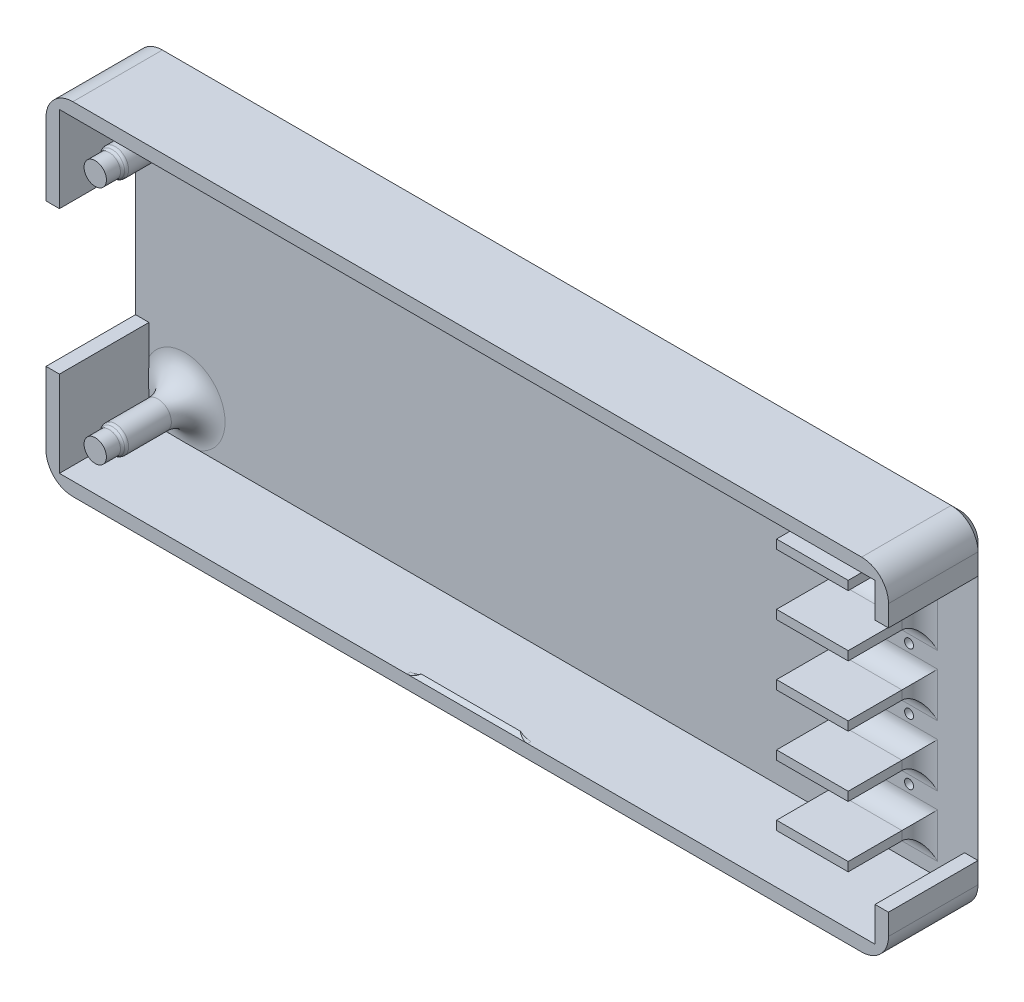
SolidWorks part; units mm, degrees
ref_plane "Front Plane" through (0, 0, 0) normal (0, 0, 1) x (1, 0, 0)
ref_plane "Top Plane" through (0, 0, 0) normal (0, 1, 0) x (1, 0, 0)
ref_plane "Right Plane" through (0, 0, 0) normal (1, 0, 0) x (0, 0, -1)
sketch "Sketch1" plane through (0, 0, 0) normal (0, 0, 1) x (1, 0, 0)
  line L0 (-1.5, 36.7) -> (92.6, 36.7)
  line L1 (0, 0) -> (91.1, 0)
  line L2 (0, 0) -> (0, 35.2)
  line L3 (0, 35.2) -> (91.1, 35.2)
  line L4 (91.1, 0) -> (91.1, 35.2)
  line L5 (92.6, -1.5) -> (92.6, 36.7)
  line L6 (-1.5, -1.5) -> (92.6, -1.5)
  line L7 (-1.5, -1.5) -> (-1.5, 36.7)
  dimension "D1" = 91.1
  dimension "D2" = 35.2
  dimension "D3" = 1.5
extrude "Boss-Extrude1" add sketch "Sketch1" along normal blind 1 contours L1 L4 L3 L2 | L7 L6 L5 L0 L4 L1 L2 L3 region at (45.55, 35.6844, 0) region at (45.55, 17.6, 0)
extrude "Boss-Extrude2" add sketch "Sketch1<3>" along normal blind 11
sketch "Sketch1<3>" plane through (0, 0, 0) normal (0, 0, 1) x (1, 0, 0) same geometry as "Sketch1"
sketch "Sketch2" plane through (0, 0, 11) normal (0, 0, 1) x (1, 0, 0)
  line L0 (-1.5, 36.7) -> (-1.5, -1.5) construction
  line L1 (-1.5, 25.6) -> (0, 25.6)
  line L2 (-1.5, 25.6) -> (-1.5, 9.6)
  line L3 (-1.5, 9.6) -> (0, 9.6)
  line L4 (0, 25.6) -> (0, 9.6)
  line L5 (92.6, -1.5) -> (92.6, 36.7) construction
  line L6 (92.6, 31.35) -> (91.1, 31.35)
  line L7 (92.6, 31.35) -> (92.6, 3.85)
  line L8 (92.6, 3.85) -> (91.1, 3.85)
  line L9 (91.1, 31.35) -> (91.1, 3.85)
  line L10 (-0.75, 25.6) -> (-0.75, 35.2) construction
  line L12 (-0.75, 9.6) -> (-0.75, 0) construction
  line L13 (91.1, 0) -> (0, 0) construction
  line L14 (91.85, 3.85) -> (91.85, 0) construction
  line L15 (91.85, 31.35) -> (91.85, 35.2) construction
  line L16 (91.1, 35.2) -> (0, 35.2) construction
  line L17 (0, 35.2) -> (0, 0) construction
  line L18 (91.1, 0) -> (91.1, 35.2) construction
  dimension "D1" = 16
  dimension "D2" = 27.5
extrude "Cut-Extrude1" cut sketch "Sketch2" against normal blind 10
sketch "Sketch3" plane through (0, 0, 1) normal (0, 0, 1) x (1, 0, 0)
  line L0 (92.6, 3.85) -> (92.6, 31.35) construction
  line L1 (78.1, 31.7) -> (86.1, 31.7)
  line L2 (78.1, 31.7) -> (78.1, 30.7)
  line L3 (78.1, 30.7) -> (86.1, 30.7)
  line L4 (86.1, 31.7) -> (86.1, 30.7)
  line L5 (0, 35.2) -> (91.1, 35.2) construction
  line L6 (78.1, 24.9) -> (86.1, 24.9)
  line L7 (78.1, 24.9) -> (78.1, 23.9)
  line L8 (78.1, 23.9) -> (86.1, 23.9)
  line L9 (86.1, 24.9) -> (86.1, 23.9)
  line L10 (78.1, 18.1) -> (86.1, 18.1)
  line L11 (78.1, 18.1) -> (78.1, 17.1)
  line L12 (78.1, 17.1) -> (86.1, 17.1)
  line L13 (86.1, 18.1) -> (86.1, 17.1)
  line L15 (78.1, 11.3) -> (86.1, 11.3)
  line L16 (78.1, 11.3) -> (78.1, 10.3)
  line L17 (78.1, 10.3) -> (86.1, 10.3)
  line L18 (86.1, 11.3) -> (86.1, 10.3)
  line L19 (78.1, 4.5) -> (86.1, 4.5)
  line L20 (78.1, 4.5) -> (78.1, 3.5)
  line L21 (78.1, 3.5) -> (86.1, 3.5)
  line L22 (86.1, 4.5) -> (86.1, 3.5)
  line L23 (91.1, 0) -> (0, 0) construction
  dimension "D1" = 1
  dimension "D2" = 6.5
  dimension "D3" = 3.5
  dimension "D4" = 8
  dimension "D6" = 3.5
  dimension "D7" = 6.8
  dimension "D5" = 5
extrude "Boss-Extrude3" add sketch "Sketch3" along normal blind 8
sketch "Sketch4" plane through (0, 0, 1) normal (0, 0, 1) x (1, 0, 0)
  line L0 (84.9, 35.2) -> (84.9, 0) construction
  line L1 (91.1, 35.2) -> (0, 35.2) construction
  line L2 (0, 0) -> (91.1, 0) construction
  line L5 (86.1, 31.7) -> (78.1, 31.7) construction
  line L7 (92.6, 3.85) -> (92.6, 31.35) construction
  line L8 (84.9, 7.4) -> (86.1, 4.5) construction
  line L9 (84.9, 7.4) -> (86.1, 10.3) construction
  line L10 (84.9, 27.8) -> (86.1, 24.9) construction
  line L11 (84.9, 27.8) -> (86.1, 30.7) construction
  circle A0 centre (84.9, 27.8) radius 0.5
  circle A1 centre (84.9, 21) radius 0.5
  circle A2 centre (84.9, 14.2) radius 0.5
  circle A3 centre (84.9, 7.4) radius 0.5
  dimension "D1" = 1
  dimension "D6" = 3.9
  dimension "D9" = 7.7
  dimension "D10" = 6.8
  dimension "D11" = 6.8
  dimension "D3" = 4
extrude "Cut-Extrude2" cut sketch "Sketch4" against normal blind 10
sketch "Sketch5" plane through (0, 0, 1) normal (0, 0, 1) x (1, 0, 0)
  line L0 (4, 35.2) -> (4, 0) construction
  line L1 (91.1, 35.2) -> (0, 35.2) construction
  line L2 (0, 0) -> (91.1, 0) construction
  line L4 (0, 35.2) -> (0, 25.6) construction
  line L5 (0, 35.2) -> (91.1, 35.2) construction
  line L6 (91.1, 0) -> (0, 0) construction
  circle A0 centre (4, 31) radius 1.5
  circle A1 centre (4, 4.2) radius 1.5
  dimension "D4" = 3
  dimension "D1" = 4
  dimension "D2" = 4.2
  dimension "D3" = 4.2
extrude "Boss-Extrude4" add sketch "Sketch5" along normal blind 8
sketch "Sketch7" plane through (0, 0, 9) normal (0, 0, 1) x (1, 0, 0)
  circle A0 centre (4, 31) radius 1.25
  circle A1 centre (4, 4.2) radius 1.25
  circle A2 centre (4, 31) radius 1.5 construction
  circle A3 centre (4, 4.2) radius 1.5 construction
  dimension "D1" = 2.5
extrude "Boss-Extrude6" add sketch "Sketch7" along normal blind 2
fillet "Fillet1" radius 3 2 edges at (5.5, 4.2, 1) (5.5, 31, 1)
fillet "Fillet2" radius 2 20 edges at (78.1, 31.2, 1) (82.1, 30.7, 1) (86.1, 31.2, 1) (82.1, 31.7, 1) (78.1, 4, 1) (82.1, 3.5, 1) (86.1, 4, 1) (78.1, 10.8, 1) (82.1, 10.3, 1) (86.1, 10.8, 1) (82.1, 11.3, 1) (78.1, 17.6, 1) (82.1, 17.1, 1) (86.1, 17.6, 1) (82.1, 18.1, 1) (78.1, 24.4, 1) (82.1, 23.9, 1) (86.1, 24.4, 1) (82.1, 24.9, 1) (82.1, 4.5, 1)
fillet "Fillet3" radius 3 4 edges at (-1.5, 36.7, 5.5) (92.6, 36.7, 5.5) (-1.5, -1.5, 5.5) (92.6, -1.5, 5.5)
chamfer "Chamfer2" distance 1 angle 45 8 edges at (-1.5, 17.6, 0) (-0.6213, -0.6213, 0) (-0.6213, 35.8213, 0) (45.55, -1.5, 0) (45.55, 36.7, 0) (91.7213, -0.6213, 0) (91.7213, 35.8213, 0) (92.6, 17.6, 0)
sketch "Sketch6" plane through (0, 35.2, 0) normal (0, -1, 0) x (1, 0, 0)
  line L0 (1.5, 11) -> (89.6, 11) construction
  line L1 (40.55, 11) -> (50.55, 11)
  line L2 (40.55, 11) -> (40.55, 10.6)
  line L3 (40.55, 10.6) -> (50.55, 10.6)
  line L4 (50.55, 11) -> (50.55, 10.6)
  line L5 (-1.5, 10.8) -> (40.55, 10.8) construction
  line L6 (-1.5, 1) -> (-1.5, 11) construction
  line L7 (50.55, 10.8) -> (92.6, 10.8) construction
  line L8 (92.6, 11) -> (92.6, 1) construction
  line L9 (5.6155, 1) -> (91.1, 1) construction
  dimension "D1" = 9.6
  dimension "D2" = 10
extrude "Boss-Extrude5" add sketch "Sketch6" along normal blind 1
fillet "Fillet4" radius 2 2 edges at (40.55, 35.2, 10.8) (50.55, 35.2, 10.8)
chamfer "Chamfer3" distance 1 angle 45 1 edges at (45.55, 34.2, 11)
fillet "Fillet5" radius 0.5 2 edges at (5.25, 4.2, 9) (5.25, 31, 9)
fillet "Fillet6" radius 0.5 2 edges at (5.5, 4.2, 9) (5.5, 31, 9)
ref_plane "Plane1" through (0, 17.6, 0) normal (0, -1, 0) x (-1, 0, 0)
mirror "Mirror2" about plane through (0, 17.6, 0) normal (0, -1, 0) of "Boss-Extrude5", "Fillet4", "Chamfer3"
